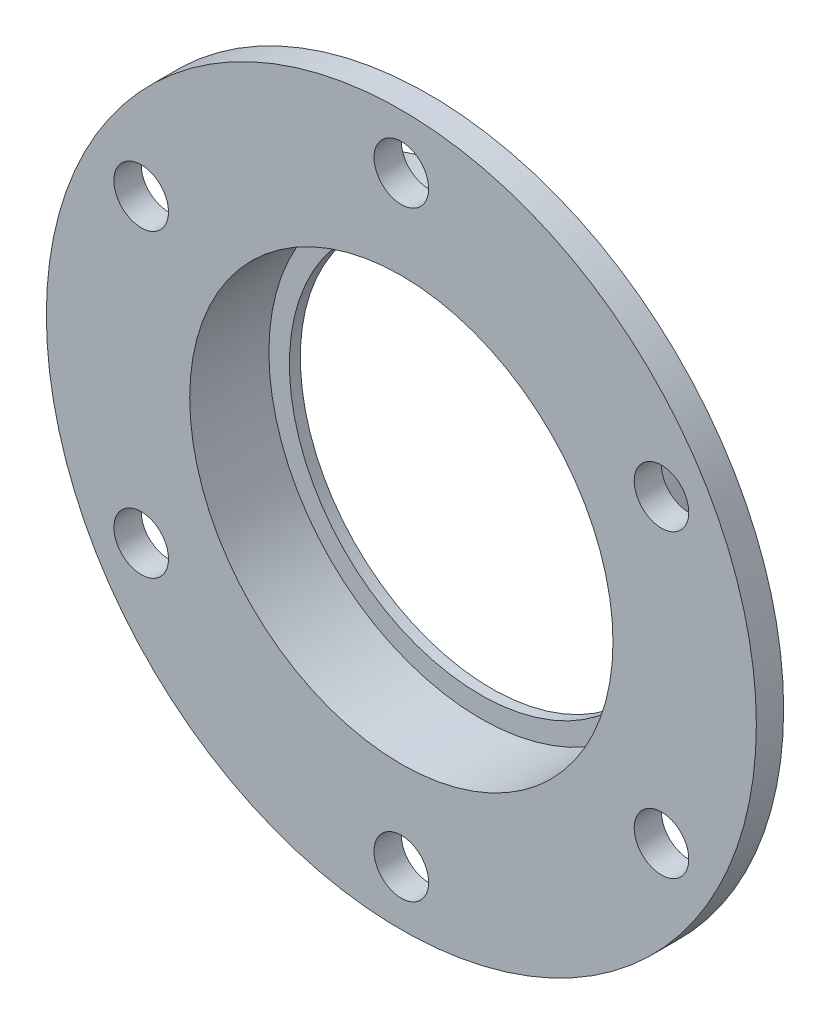
SolidWorks part; units mm, degrees
ref_plane "Front Plane" through (0, 0, 0) normal (0, 0, 1) x (1, 0, 0)
ref_plane "Top Plane" through (0, 0, 0) normal (0, 1, 0) x (1, 0, 0)
ref_plane "Right Plane" through (0, 0, 0) normal (1, 0, 0) x (0, 0, -1)
sketch "Sketch1" plane through (0, 0, 0) normal (0, 0, 1) x (1, 0, 0)
  circle A0 centre (0, 0) radius 45
  dimension "D1" = 90
extrude "Boss-Extrude1" add sketch "Sketch1" along normal blind 16.5
sketch "Sketch2" plane through (0, 0, 16.5) normal (0, 0, 1) x (1, 0, 0)
  circle A0 centre (0, 0) radius 38.75
  dimension "D1" = 77.5
extrude "Cut-Extrude1" cut sketch "Sketch2" against normal offset from surface (14.5 mm away) 2 up to face at (45, 0, 0)
sketch "Sketch3" plane through (0, 0, 2) normal (0, 0, 1) x (1, 0, 0)
  circle A0 centre (0, 0) radius 35
  dimension "D1" = 70
extrude "Cut-Extrude2" cut sketch "Sketch3" against normal through all
sketch "Sketch4" plane through (0, 0, 16.5) normal (0, 0, 1) x (1, 0, 0)
  circle A0 centre (0, 0) radius 65
  circle A1 centre (0, 0) radius 45
  circle A2 centre (0, 0) radius 45 construction
  dimension "D1" = 20
extrude "Boss-Extrude2" add sketch "Sketch4" against normal blind 5
sketch "Sketch5" plane through (0, 0, 11.5) normal (0, 0, -1) x (-1, 0, 0)
  circle A0 centre (0, 0) radius 55 construction
  circle A1 centre (0, 55) radius 5
  circle A2 centre (0, 0) radius 55 construction
  circle A3 centre (47.6314, 27.5) radius 5
  circle A4 centre (0, 0) radius 55 construction
  circle A5 centre (47.6314, -27.5) radius 5
  circle A6 centre (0, 0) radius 55 construction
  circle A7 centre (0, -55) radius 5
  circle A8 centre (0, 0) radius 55 construction
  circle A9 centre (-47.6314, -27.5) radius 5
  circle A10 centre (0, 0) radius 55 construction
  circle A11 centre (-47.6314, 27.5) radius 5
  point P23 (0, 0)
  dimension "D1" = 110
  dimension "D2" = 10
  dimension "D3" = 6
extrude "Cut-Extrude3" cut sketch "Sketch5" against normal through all
